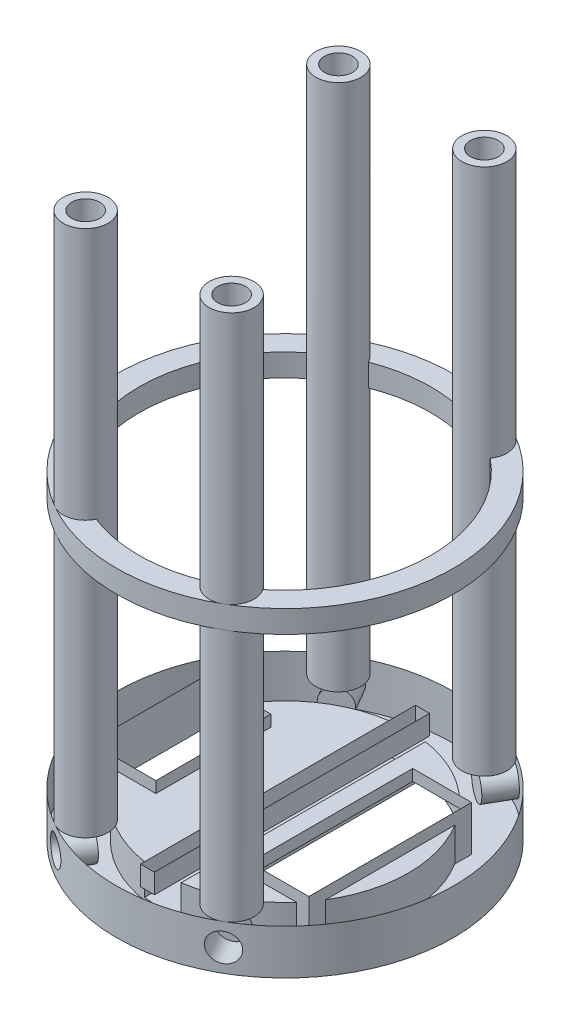
SolidWorks part; units mm, degrees
ref_plane "前基準面" through (0, 0, 0) normal (0, 0, 1) x (1, 0, 0)
ref_plane "上基準面" through (0, 0, 0) normal (0, 1, 0) x (1, 0, 0)
ref_plane "右基準面" through (0, 0, 0) normal (1, 0, 0) x (0, 0, -1)
sketch "草圖1" plane through (0, 0, 0) normal (0, 1, 0) x (1, 0, 0)
  line L0 (-24, 0) -> (24, 0) construction
  line L9 (0, 24) -> (0, -24) construction
  line L15 (-1, 19.6) -> (1, 19.6)
  line L16 (-1, 19.6) -> (-1, -19.6)
  line L17 (-1, -19.6) -> (1, -19.6)
  line L18 (1, 19.6) -> (1, -19.6)
  line L19 (-13.4, 5) -> (-16.4, 5)
  line L20 (-16.4, 5) -> (-16.4, -5)
  line L21 (-16.4, -5) -> (-13.4, -5)
  line L22 (-13.4, 5) -> (-13.4, -5)
  line L23 (0, 0) -> (-10.4, 18.0133) construction
  line L24 (9.8, 10) -> (11.8, 10)
  line L25 (9.8, 10) -> (9.8, -10)
  line L26 (9.8, -10) -> (11.8, -10)
  line L27 (11.8, 10) -> (11.8, -10)
  line L28 (0, 0) -> (10.4, 18.0133) construction
  line L29 (0, 0) -> (10.4, -18.0133) construction
  line L30 (0, 0) -> (-10.4, -18.0133) construction
  line L31 (-2.6, 21.2) -> (2.6, 21.2)
  line L32 (-2.6, 21.2) -> (-2.6, -21.2)
  line L33 (-2.6, -21.2) -> (2.6, -21.2)
  line L34 (2.6, 21.2) -> (2.6, -21.2)
  line L35 (6.6, 11.6) -> (15, 11.6)
  line L36 (6.6, 11.6) -> (6.6, -11.6)
  line L37 (6.6, -11.6) -> (15, -11.6)
  line L38 (15, 11.6) -> (15, -11.6)
  line L39 (-10.2, -8.2) -> (-19.6, -8.2)
  line L40 (-10.2, -8.2) -> (-10.2, 8.2)
  line L41 (-10.2, 8.2) -> (-19.6, 8.2)
  line L42 (-19.6, -8.2) -> (-19.6, 8.2)
  circle A0 centre (0, 0) radius 24
  circle A4 centre (-10.4, 18.0133) radius 3.2
  circle A9 centre (0, 0) radius 20.8
  arc A11 (-23.7808, 3.2365) -> (-23.7808, -3.2365) centre (0, 0) ccw
  arc A12 (-23.7808, 3.2365) -> (-23.7808, -3.2365) centre (0, 0) cw
  arc A15 (14.6933, 18.9765) -> (9.0875, 22.213) centre (0, 0) ccw
  arc A17 (23.7808, -3.2365) -> (23.7808, 3.2365) centre (0, 0) ccw
  arc A30 (23.9346, -1.7704) -> (23.9346, 1.7704) centre (0, 0) ccw
  arc A32 (10.4341, -21.6132) -> (13.5005, -19.8428) centre (0, 0) ccw
  arc A34 (-13.5005, -19.8428) -> (-10.4341, -21.6132) centre (0, 0) ccw
  circle A35 centre (0, 0) radius 17.6
  arc A36 (-14.6933, -18.9765) -> (-9.0875, -22.213) centre (0, 0) ccw [skipped]
  arc A38 (9.0875, 22.213) -> (14.6933, 18.9765) centre (0, 0) cw
  circle A41 centre (10.4, 18.0133) radius 3.2
  arc A43 (10.4341, -21.6132) -> (13.5005, -19.8428) centre (0, 0) ccw
  circle A44 centre (10.4, -18.0133) radius 3.2
  arc A48 (-10.4341, -21.6132) -> (-13.5005, -19.8428) centre (0, 0) cw
  circle A50 centre (-10.4, -18.0133) radius 3.2
  arc A51 (-9.0875, 22.213) -> (-14.6933, 18.9765) centre (0, 0) ccw [skipped]
  arc A52 (9.0875, -22.213) -> (14.6933, -18.9765) centre (0, 0) ccw [skipped]
  point P39 (0, 0)
  point P56 (0, 0)
  point P74 (0, 0)
  dimension "D6" = 48
  dimension "D9" = 6.4
  dimension "D10" = 60
  dimension "D11" = 7.2
  dimension "D13" = 3.2
  dimension "D15" = 1.6
  dimension "D2" = 1.6
  dimension "D3" = 1.6
  dimension "D4" = 1.6
  dimension "D5" = 1.6
  dimension "D7" = 2
  dimension "D8" = 39.2
  dimension "D16" = 10
  dimension "D17" = 3
  dimension "D18" = 20
  dimension "D19" = 2
  dimension "D14" = 3.2
  dimension "D20" = 1.6
  dimension "D21" = 10.8
  dimension "D22" = 3.2
  dimension "D23" = 3.2
  dimension "D24" = 3.2
  dimension "D25" = 3.2
  dimension "D12" = 6
extrude "填料-伸長1" add sketch "草圖1" against normal blind 1.6 contours A35
extrude "填料-伸長2" add sketch "草圖1<3>" against normal blind 6.4 contours A0 | A35
sketch "草圖1<3>" plane through (0, 0, 0) normal (0, 1, 0) x (1, 0, 0) same geometry as "草圖1"
extrude "填料-伸長3" add sketch "草圖1<4>" against normal blind 6 contours L32 L33 L34 L31
sketch "草圖1<4>" plane through (0, 0, 0) normal (0, 1, 0) x (1, 0, 0) same geometry as "草圖1"
extrude "除料-伸長1" cut sketch "草圖1<5>" against normal blind 2.8 contours L18 L17 L16 L15
sketch "草圖1<5>" plane through (0, 0, 0) normal (0, 1, 0) x (1, 0, 0) same geometry as "草圖1"
extrude "除料-伸長2" cut sketch "草圖1<6>" against normal blind 10 contours L40 L41 L42 L39 | L38 L37 L36 L35
sketch "草圖1<6>" plane through (0, 0, 0) normal (0, 1, 0) x (1, 0, 0) same geometry as "草圖1"
extrude "填料-伸長4" add sketch "草圖1<7>" along normal blind 75.2 contours A4 | A41 | A50 | A44
sketch "草圖1<7>" plane through (0, 0, 0) normal (0, 1, 0) x (1, 0, 0) same geometry as "草圖1"
ref_plane "平面1" through (0, 37.6, 0) normal (0, 1, 0) x (1, 0, 0)
sketch "草圖2" plane through (0, 37.6, 0) normal (0, 1, 0) x (1, 0, 0)
  circle A0 centre (0, 0) radius 24 construction
  circle A1 centre (0, 0) radius 20.8 construction
  circle A2 centre (0, 0) radius 24
  circle A3 centre (0, 0) radius 20.8
extrude "填料-伸長5" add sketch "草圖2" along normal blind 1.6 and the other way blind 1.6
sketch "草圖3" plane through (0, 75.2, 0) normal (0, 1, 0) x (1, 0, 0)
  line L0 (0, 0) -> (0, 6.1801) construction
  line L1 (0, 0) -> (5.0731, 0) construction
  circle A1 centre (-10.4, 18.0133) radius 3.2 construction
  circle A4 centre (-10.4, 18.0133) radius 3.2
  circle A5 centre (-10.4, 18.0133) radius 2
  circle A6 centre (10.4, 18.0133) radius 2
  circle A7 centre (10.4, -18.0133) radius 2
  circle A8 centre (-10.4, -18.0133) radius 2
  dimension "D1" = 4
extrude "除料-伸長3" cut sketch "草圖3" against normal blind 4 contours A5 | A6 | A7 | A8 region at (-10.4, 75.2, -18.0133) region at (10.4, 75.2, -18.0133) region at (10.4, 75.2, 18.0133) region at (-10.4, 75.2, 18.0133)
ref_axis "基準軸1" through (0, 0, 0) along (-0.5, 0, -0.866)
ref_plane "平面2" through (-12, 0, -20.7846) normal (-0.5, 0, -0.866) x (-0.866, 0, 0.5)
sketch "草圖4" plane through (-12, 0, -20.7846) normal (-0.5, 0, -0.866) x (-0.866, 0, 0.5)
  circle A0 centre (0, -3.2) radius 2
  point P2 (0, 0)
  dimension "D1" = 4
  dimension "D2" = 3.2
extrude "除料-伸長4" cut sketch "草圖4" against normal blind 4
mirror "鏡射1" about plane through (0, 0, 0) normal (1, 0, 0) of "除料-伸長4"
mirror "鏡射2" about plane through (0, 0, 0) normal (0, 0, 1) of "鏡射1"
